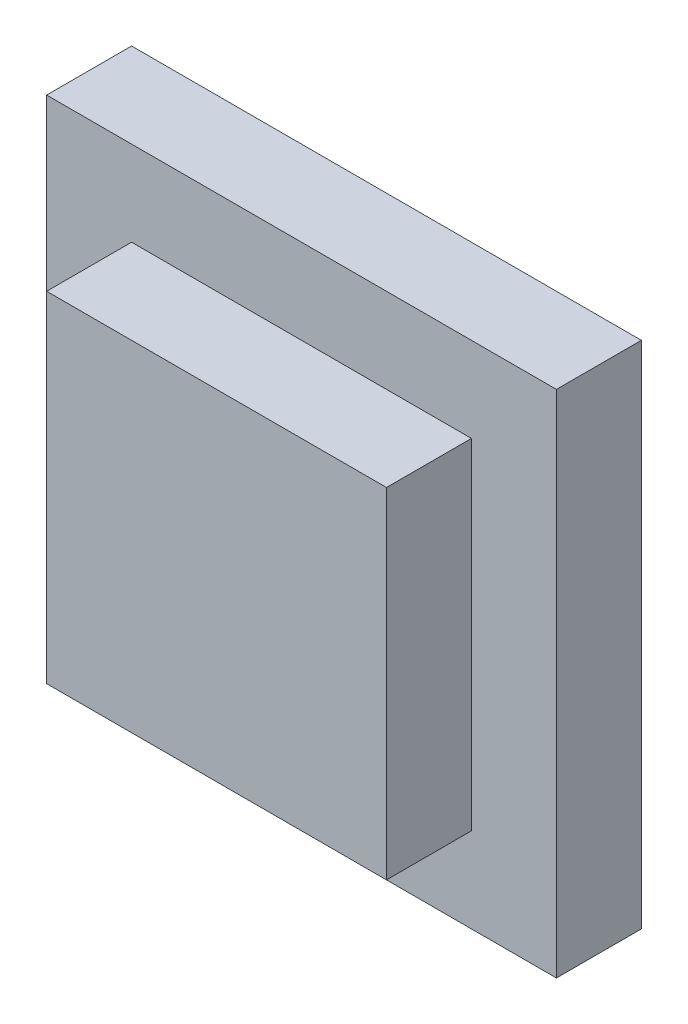
SolidWorks part; units mm, degrees
ref_plane "Front Plane" through (0, 0, 0) normal (0, 0, 1) x (1, 0, 0)
ref_plane "Top Plane" through (0, 0, 0) normal (0, 1, 0) x (1, 0, 0)
ref_plane "Right Plane" through (0, 0, 0) normal (1, 0, 0) x (0, 0, -1)
sketch "Sketch1" plane through (0, 0, 0) normal (0, 0, 1) x (1, 0, 0)
  line L1 (-4, -4) -> (4, -4)
  line L2 (-4, -4) -> (-4, 4)
  line L3 (-4, 4) -> (4, 4)
  line L4 (4, -4) -> (4, 4)
  line L5 (-4, -4) -> (4, 4) construction
  line L6 (-4, 4) -> (4, -4) construction
  line L7 (-6, -6) -> (6, -6)
  line L8 (-6, -6) -> (-6, 6)
  line L9 (-6, 6) -> (6, 6)
  line L10 (6, -6) -> (6, 6)
  line L11 (-6, -6) -> (6, 6) construction
  line L12 (-6, 6) -> (6, -6) construction
  point P0 (0, 0)
  point P6 (0, 0)
  dimension "D1" = 8
  dimension "D2" = 12
extrude "Notch" add sketch "Sketch1" along normal blind 4 contours L1 L4 L3 L2 region at (0, 0, 0)
extrude "Base" add sketch "Sketch1<3>" along normal blind 2
sketch "Sketch1<3>" plane through (0, 0, 0) normal (0, 0, 1) x (1, 0, 0) same geometry as "Sketch1"
